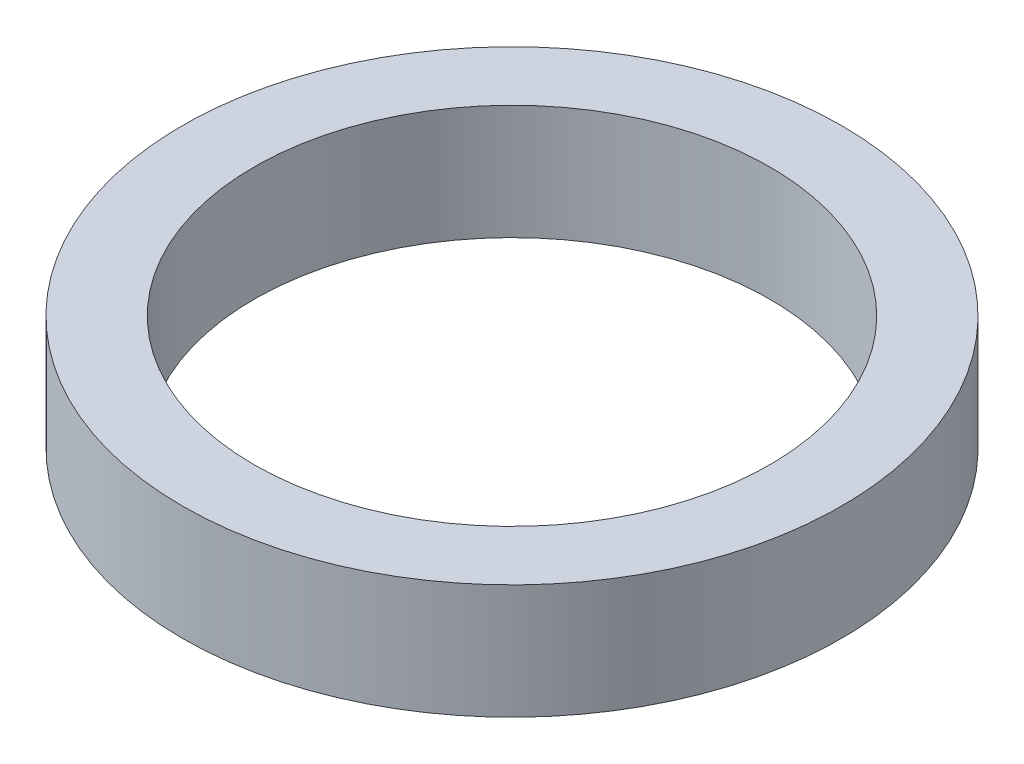
SolidWorks part; units mm, degrees
ref_plane "Front Plane" through (0, 0, 0) normal (0, 0, 1) x (1, 0, 0)
ref_plane "Top Plane" through (0, 0, 0) normal (0, 1, 0) x (1, 0, 0)
ref_plane "Right Plane" through (0, 0, 0) normal (1, 0, 0) x (0, 0, -1)
sketch "Sketch1" plane through (0, 0, 0) normal (0, 1, 0) x (1, 0, 0)
  circle A0 centre (0, 0) radius 57.5
  dimension "FLANGE_OD" = 115
extrude "Boss-Extrude1" add sketch "Sketch1" along normal blind 20
sketch "Sketch2" plane through (0, 0, 0) normal (0, 1, 0) x (1, 0, 0)
  circle A0 centre (0, 0) radius 45
  dimension "BORE_D" = 90
extrude "Cut-Extrude1" cut sketch "Sketch2" along normal through all
sketch "Sketch3" plane through (0, 20, 0) normal (0, 1, 0) x (1, 0, 0)
  circle A0 centre (0, 0) radius 26.885 construction
  circle A1 centre (-26.885, 0) radius 1.9899
  dimension "BOLT_D" = 3.9797
  dimension "BOLT_PCD" = 53.77
extrude "Cut-Extrude2" cut sketch "Sketch3" against normal blind 18.4321 rebuild error yes
pattern_circular "CirPattern1" count 3 over 360 rebuild error yes
